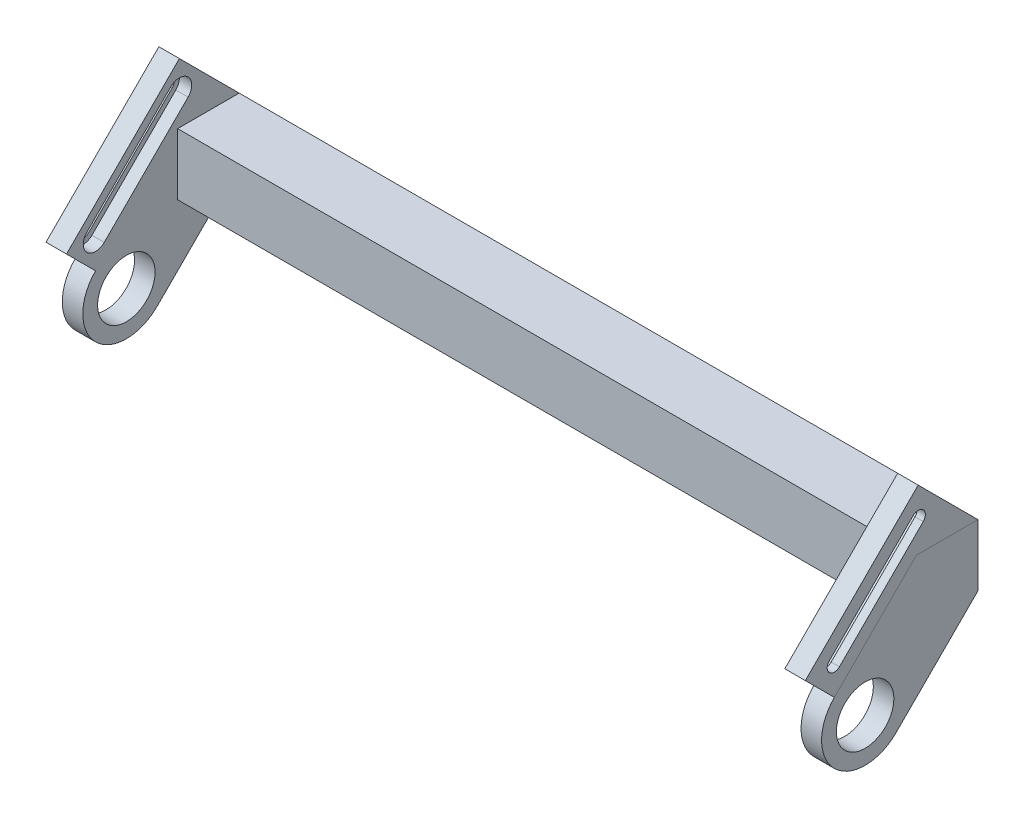
SolidWorks part; units mm, degrees
ref_plane "前视基准面" through (0, 0, 0) normal (0, 0, 1) x (1, 0, 0)
ref_plane "上视基准面" through (0, 0, 0) normal (0, 1, 0) x (1, 0, 0)
ref_plane "右视基准面" through (0, 0, 0) normal (1, 0, 0) x (0, 0, -1)
sketch "草图1" plane through (0, 0, 0) normal (1, 0, 0) x (0, 0, -1)
  line L0 (12.5, 12.5) -> (15, 15)
  line L5 (15, 15) -> (25, 15) construction
  line L6 (15, 15) -> (15, 25)
  line L7 (15, 25) -> (25, 25)
  line L8 (25, 15) -> (25, 25)
  line L9 (15, 15) -> (25, 25) construction
  line L10 (15, 25) -> (25, 15) construction
  line L11 (12.5, 12.5) -> (27.5, 12.5) construction
  line L12 (12.5, 12.5) -> (12.5, 27.5)
  line L13 (12.5, 27.5) -> (27.5, 27.5)
  line L14 (27.5, 12.5) -> (27.5, 27.5)
  line L15 (12.5, 12.5) -> (27.5, 27.5) construction
  line L16 (12.5, 27.5) -> (27.5, 12.5) construction
  line L17 (25, 15) -> (27.5, 12.5)
  point P0 (20, 20)
  point P1 (20, 20)
  point P7 (20, 20)
  dimension "D1" = 20
  dimension "D2" = 20
  dimension "D3" = 10
  dimension "D4" = 15
extrude "凸台-拉伸1" add sketch "草图1" along normal blind 87.5 and the other way blind 87.5 contours L13 L14 L17 L8 L7 L6 L0 L12
sketch "草图2" plane through (87.5, 0, 0) normal (1, 0, 0) x (0, 0, -1)
  line L0 (-7.5, 7.5) -> (12.5, 27.5)
  line L1 (12.5, 27.5) -> (27.5, 27.5)
  line L2 (27.5, 27.5) -> (27.5, 12.5)
  line L3 (27.5, 12.5) -> (7.5, -7.5)
  circle A0 centre (0, 0) radius 7
  arc A1 (-7.5, 7.5) -> (7.5, -7.5) centre (0, 0) ccw
  dimension "D1" = 14
extrude "凸台-拉伸2" add sketch "草图2" along normal blind 5
mirror "镜向4" about plane through (0, 0, 0) normal (1, 0, 0) of "凸台-拉伸2"
sketch "草图3" plane through (92.5, 0, 0) normal (1, 0, 0) x (0, 0, -1)
  line L3 (27.5, 27.5) -> (12.9289, 42.0711)
  line L4 (12.9289, 42.0711) -> (-14.5711, 14.5711)
  line L5 (-14.5711, 14.5711) -> (-7.5, 7.5)
  line L6 (-7.5, 7.5) -> (12.5, 27.5)
  line L7 (12.5, 27.5) -> (27.5, 27.5)
  line L8 (12.5, 27.5) -> (-7.5, 7.5) construction
  line L9 (-7.5, 14.5711) -> (-11.0355, 11.0355) construction
  dimension "D1" = 45
  dimension "D2" = 10
extrude "凸台-拉伸3" add sketch "草图3" against normal blind 5 separate body
sketch "草图4" plane through (92.5, 0, 0) normal (1, 0, 0) x (0, 0, -1)
  line L0 (-7.5, 14.5711) -> (12.9289, 35) construction
  line L1 (-8.7374, 15.8085) -> (11.6915, 36.2374)
  line L2 (-6.2626, 13.3336) -> (14.1664, 33.7626)
  line L3 (-7.5, 14.5711) -> (-11.0355, 11.0355) construction
  line L4 (-14.5711, 14.5711) -> (-7.5, 7.5) construction
  line L5 (12.9289, 42.0711) -> (-14.5711, 14.5711) construction
  line L6 (27.5, 27.5) -> (12.9289, 42.0711) construction
  arc A0 (-8.7374, 15.8085) -> (-6.2626, 13.3336) centre (-7.5, 14.5711) ccw
  arc A1 (14.1664, 33.7626) -> (11.6915, 36.2374) centre (12.9289, 35) ccw
  point P2 (2.7145, 24.7855)
  dimension "D1" = 3.5
  dimension "D2" = 5
  dimension "D3" = 5
extrude "切除-拉伸1" cut sketch "草图4" against normal blind 10
sketch "草图5" plane through (87.5, 0, 0) normal (-1, 0, 0) x (0, 0, 1)
  line L0 (-12.9289, 35) -> (7.5, 14.5711) construction
  line L1 (-10.8076, 37.1213) -> (9.6213, 16.6924)
  line L2 (-15.0503, 32.8787) -> (5.3787, 12.4497)
  arc A0 (-10.8076, 37.1213) -> (-15.0503, 32.8787) centre (-12.9289, 35) ccw
  arc A1 (5.3787, 12.4497) -> (9.6213, 16.6924) centre (7.5, 14.5711) ccw
  point P4 (-2.7145, 24.7855)
  dimension "D1" = 6
extrude "切除-拉伸2" cut sketch "草图5" against normal blind 3
mirror "镜向7" about plane through (0, 0, 0) normal (1, 0, 0) of "凸台-拉伸3", "切除-拉伸1", "切除-拉伸2"
